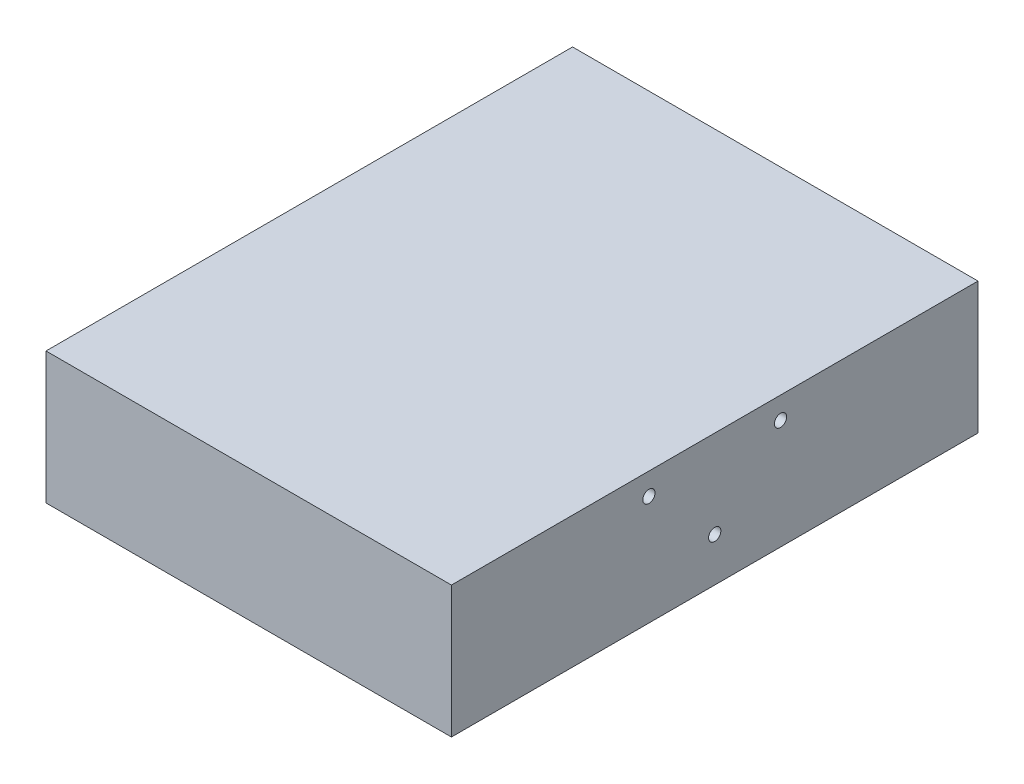
SolidWorks part; units mm, degrees
material "Copper"
ref_plane "Front Plane" through (0, 0, 0) normal (0, 0, 1) x (1, 0, 0)
ref_plane "Top Plane" through (0, 0, 0) normal (0, 1, 0) x (1, 0, 0)
ref_plane "Right Plane" through (0, 0, 0) normal (1, 0, 0) x (0, 0, -1)
sketch "Sketch1" plane through (0, 0, 0) normal (0, 0, 1) x (1, 0, 0)
  line L1 (0, 0) -> (-117.348, 0)
  line L2 (0, 0) -> (0, -38.1)
  line L3 (0, -38.1) -> (-117.348, -38.1)
  line L4 (-117.348, 0) -> (-117.348, -38.1)
  dimension "D1" = 117.348
  dimension "D2" = 38.1
extrude "Boss-Extrude1" add sketch "Sketch1" along normal blind 152.4
sketch "Sketch2" plane through (0, 0, 0) normal (1, 0, 0) x (0, 0, -1)
  line L0 (-76.2, 0) -> (-76.2, -38.1)
  line L1 (-152.4, 0) -> (0, 0) construction
  line L2 (-152.4, -38.1) -> (0, -38.1) construction
  circle A0 centre (-95.25, -6.35) radius 1.778
  circle A1 centre (-57.15, -6.35) radius 1.778
  circle A2 centre (-76.2, -25.4) radius 1.778
  dimension "D1" = 3.556
  dimension "D2" = 3.556
  dimension "D8" = 3.556
  dimension "D3" = 31.75
  dimension "D4" = 31.75
  dimension "D5" = 19.05
  dimension "D6" = 19.05
  dimension "D7" = 19.05
extrude "Cut-Extrude1" cut sketch "Sketch2" against normal blind 152.4 contours A0 | L0 A2 | A1 | A2 region at (0, -25.4, 76.9546) region at (0, -6.35, 95.25) region at (0, -6.35, 57.15)
sketch "Sketch3" plane through (0, 0, 0) normal (1, 0, 0) x (0, 0, -1)
  line L0 (-76.2, 0) -> (-76.2, -38.1) construction
  line L1 (-152.4, 0) -> (0, 0) construction
  line L2 (-152.4, -38.1) -> (0, -38.1) construction
  circle A0 centre (-76.2, -6.35) radius 6.35
  dimension "D1" = 12.7
  dimension "D2" = 31.75
